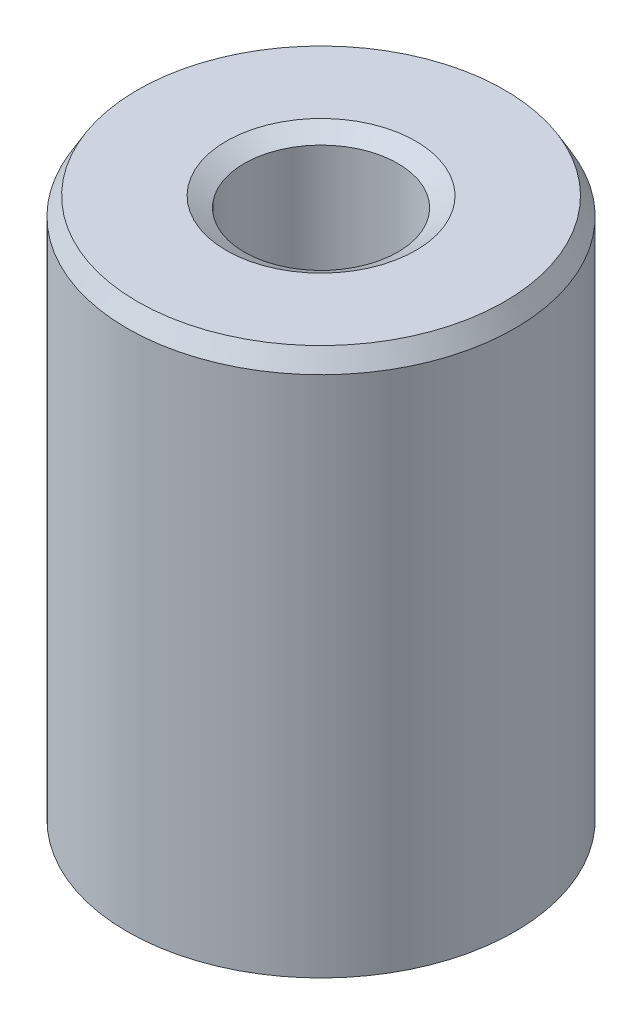
SolidWorks part; units mm, degrees
ref_plane "Front Plane" through (0, 0, 0) normal (0, 0, 1) x (1, 0, 0)
ref_plane "Top Plane" through (0, 0, 0) normal (0, 1, 0) x (1, 0, 0)
ref_plane "Right Plane" through (0, 0, 0) normal (1, 0, 0) x (0, 0, -1)
sketch "Sketch1" plane through (0, 0, 0) normal (0, 1, 0) x (1, 0, 0)
  circle A0 centre (0, 0) radius 20
  dimension "SLEEVE_OD" = 40
extrude "Boss-Extrude1" add sketch "Sketch1" along normal blind 56.8257
sketch "Sketch2" plane through (0, 0, 0) normal (0, 1, 0) x (1, 0, 0)
  circle A0 centre (0, 0) radius 7.9248
  dimension "BORE_D" = 15.8496
extrude "Cut-Extrude1" cut sketch "Sketch2" along normal through all
chamfer "Chamfer1" distance 1.8516 angle 30 4 edges at (0, 56.8257, 7.9248) (0, 0, 7.9248) (0, 0, 20) (0, 56.8257, 20) first distance on face at (0, 56.8257, 7.9248) first distance on face at (0, 0, 7.9248) first distance on face at (0, 56.8257, 20)
